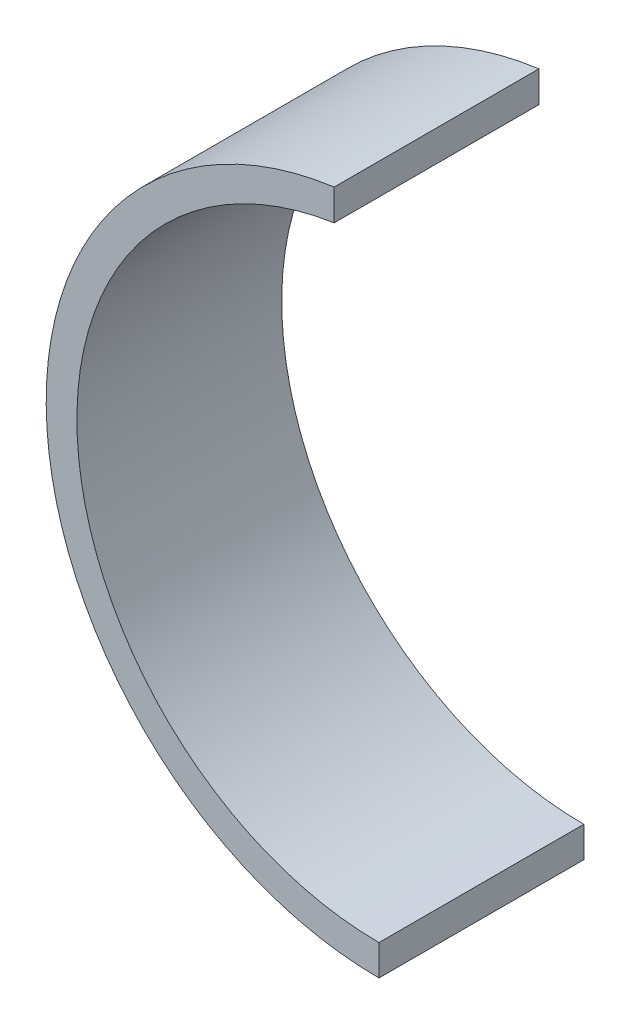
SolidWorks part; units mm, degrees
ref_plane "Front Plane" through (0, 0, 0) normal (0, 0, 1) x (1, 0, 0)
ref_plane "Top Plane" through (0, 0, 0) normal (0, 1, 0) x (1, 0, 0)
ref_plane "Right Plane" through (0, 0, 0) normal (1, 0, 0) x (0, 0, -1)
sketch "Sketch1" plane through (0, 0, 0) normal (0, 0, 1) x (1, 0, 0)
  line L1 (0, -29.5) -> (0, -32.5)
  line L2 (-4.3787, 29.1732) -> (-4.3787, 32.2037)
  arc A0 (-4.3787, 32.2037) -> (0, -32.5) centre (0, 0) ccw
  arc A1 (-4.3787, 29.1732) -> (0, -29.5) centre (0, 0) ccw
  dimension "D1" = 65
extrude "Boss-Extrude1" add sketch "Sketch1" along normal blind 20
ref_axis "Axis1" through (0, 0, 20) along (0, 0, -1)
ref_plane "Plane3" through (-0.4992, 32.4962, 0) normal (-0.0154, 0.9999, 0) x (0.9999, 0.0154, 0)
